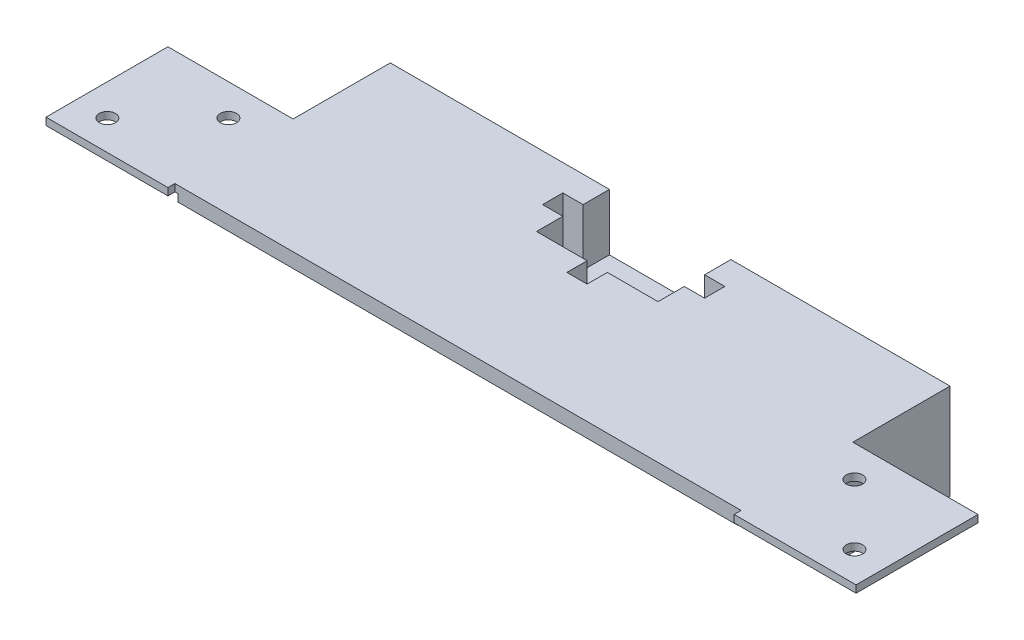
SolidWorks part; units mm, degrees
ref_plane "Alzado" through (0, 0, 0) normal (0, 0, 1) x (1, 0, 0)
ref_plane "Planta" through (0, 0, 0) normal (0, 1, 0) x (1, 0, 0)
ref_plane "Vista lateral" through (0, 0, 0) normal (1, 0, 0) x (0, 0, -1)
sketch "Croquis1" plane through (0, 0, 0) normal (0, 1, 0) x (1, 0, 0)
  line L0 (0, 16.8548) -> (0, -58.7896) construction
  line L1 (-69.5, -36.2916) -> (-69.5, -34.5716) construction
  line L2 (-100, -36.2916) -> (-69.5, -36.2916) construction
  line L3 (-100, -5.7916) -> (-100, -36.2916) construction
  line L4 (-69.5, -5.7916) -> (-100, -5.7916) construction
  line L5 (-69.5, -34.5716) -> (-69.5, -5.7916) construction
  line L17 (-69.5, -9.7916) -> (69.5, -9.7916) construction
  line L18 (69.5, -34.5716) -> (69.5, -5.7916) construction
  line L19 (69.5, -5.7916) -> (100, -5.7916) construction
  line L20 (100, -5.7916) -> (100, -36.2916) construction
  line L21 (100, -36.2916) -> (69.5, -36.2916) construction
  line L22 (69.5, -36.2916) -> (69.5, -34.5716) construction
  line L23 (69.5, -34.5716) -> (-69.5, -34.5716) construction
  circle A0 centre (-77.2782, -13.5698) radius 2 construction
  circle A1 centre (-92.2218, -28.5135) radius 2 construction
  circle A2 centre (-56.5, -26.2016) radius 2 construction
  circle A11 centre (56.5, -26.2016) radius 2 construction
  circle A12 centre (92.2218, -28.5135) radius 2 construction
  circle A13 centre (77.2782, -13.5698) radius 2 construction
  point P23 (0, -34.5716)
  point P28 (0, -9.7916)
sketch "Croquis4" plane through (0, 0, 0) normal (0, 1, 0) x (1, 0, 0)
  line L0 (69.5, -34.5716) -> (-69.5, -34.5716) construction
  line L1 (100, -36.2916) -> (69.5, -36.2916) construction
  line L2 (100, -5.7916) -> (100, -36.2916) construction
  line L3 (69.5, -5.7916) -> (100, -5.7916) construction
  line L5 (-69.5, -9.7916) -> (69.5, -9.7916) construction
  line L6 (0, 16.8548) -> (0, -58.7896) construction
  line L7 (69.5, -34.5716) -> (0, -34.5716) construction
  line L8 (100, -36.2916) -> (69.5, -36.2916) construction
  line L9 (100, -5.7916) -> (100, -36.2916) construction
  line L10 (69.5, -5.7916) -> (100, -5.7916) construction
  line L12 (0, -9.7916) -> (69.5, -9.7916) construction
  line L13 (0, 16.8548) -> (0, -58.7896) construction
  line L15 (69.5, -36.2916) -> (69.5, -34.5716) construction
  line L16 (69.5, -36.2916) -> (69.5, -34.5716) construction
  line L17 (100, -35.8916) -> (69.9, -35.8916)
  line L18 (69.9, -35.8916) -> (69.9, -34.1716)
  line L19 (69.9, -34.1716) -> (0, -34.1716)
  line L20 (100, -35.8916) -> (100, -5.7916)
  line L22 (100, -5.7916) -> (-100, -5.7916)
  line L23 (-69.9, -34.1716) -> (0, -34.1716)
  line L24 (-69.9, -35.8916) -> (-69.9, -34.1716)
  line L25 (-100, -35.8916) -> (-69.9, -35.8916)
  line L26 (-100, -35.8916) -> (-100, -5.7916)
  point P21 (0, -5.7916)
  dimension "D1" = 0.4
extrude "Saliente-Extruir1" add sketch "Croquis4" along normal blind 1.8
sketch "Croquis5" plane through (0, 1.8, 0) normal (0, 1, 0) x (1, 0, 0)
  line L0 (69.5, -34.5716) -> (-69.5, -34.5716) construction
  line L1 (69.5, -34.5716) -> (69.5, -5.7916) construction
  line L2 (-69.5, -9.7916) -> (69.5, -9.7916) construction
  line L3 (0, 16.8548) -> (0, -58.7896) construction
  line L4 (69.5, -34.5716) -> (0, -34.5716) construction
  line L5 (69.5, -34.5716) -> (69.5, -9.7916) construction
  line L6 (0, -9.7916) -> (69.5, -9.7916) construction
  line L7 (0, 16.8548) -> (0, -58.7896) construction
  line L11 (-69.1, -34.1716) -> (69.1, -34.1716)
  line L17 (-69.9, -34.1716) -> (69.9, -34.1716) construction
  line L18 (69.1, -34.1716) -> (69.1, -9.7916)
  line L19 (69.1, -34.5716) -> (69.1, -9.7916) construction
  line L20 (69.1, -9.7916) -> (69.1, -5.7916)
  line L21 (100, -5.7916) -> (-100, -5.7916) construction
  line L22 (69.1, -5.7916) -> (-69.1, -5.7916)
  line L23 (-69.1, -34.1716) -> (-69.1, -9.7916)
  line L24 (-69.1, -9.7916) -> (-69.1, -5.7916)
  point P20 (0, -10.2916)
  point P21 (0, -34.1716)
  point P23 (0, -5.7916)
  dimension "D1" = 0.4
extrude "Saliente-Extruir2" add sketch "Croquis5" against normal blind 1.8 from surface starting at face at (0, 0, 27.9366)
sketch "Croquis6" plane through (0, 1.8, 0) normal (0, 1, 0) x (1, 0, 0)
  line L0 (-69.5, -9.7916) -> (69.5, -9.7916) construction
  line L1 (0, -9.7916) -> (69.5, -9.7916) construction
  line L2 (0, 16.8548) -> (0, -58.7896) construction
  line L3 (0, 16.8548) -> (0, -58.7896) construction
  line L4 (69.5, -34.5716) -> (69.5, -5.7916) construction
  line L5 (69.5, -9.7916) -> (69.5, -5.7916) construction
  line L14 (-69.1, -9.1916) -> (69.1, -9.1916)
  line L15 (69.1, -9.1916) -> (69.1, -5.7916)
  line L16 (69.1, -9.7916) -> (69.1, -5.7916) construction
  line L17 (0, -9.1916) -> (69.5, -9.1916) construction
  line L18 (69.1, -5.7916) -> (-69.1, -5.7916)
  line L19 (100, -5.7916) -> (-100, -5.7916) construction
  line L20 (-69.1, -9.1916) -> (-69.1, -5.7916)
  point P17 (0, -5.7916)
  dimension "D1" = 0.6
  dimension "D2" = 0.4
extrude "Saliente-Extruir3" add sketch "Croquis6" against normal blind 20 from surface starting at face at (0, -1.8, 19.9816)
sketch "Croquis7" plane through (0, 0, 5.7916) normal (0, 0, -1) x (-1, 0, 0)
  line L0 (0, 22.365) -> (0, -38.5622) construction
  line L1 (0, 1.8) -> (75, 1.8)
  line L2 (-100, 1.8) -> (100, 1.8) construction
  line L3 (75, 1.8) -> (75, -21.8)
  line L4 (-69.1, -21.8) -> (69.1, -21.8) construction
  line L5 (75, -21.8) -> (0, -21.8)
  dimension "D1" = 75
sketch "Croquis8" plane through (0, 0, 5.7916) normal (0, 0, -1) x (-1, 0, 0)
  line L0 (0, 22.365) -> (0, -38.5622) construction
  line L1 (0, 22.365) -> (0, -38.5622) construction
  line L2 (-69.1, 1.8) -> (69.1, 1.8)
  line L3 (0, 1.8) -> (75, 1.8) construction
  line L4 (69.1, 1.8) -> (69.1, -21.8)
  line L5 (69.1, -21.8) -> (-69.1, -21.8)
  line L6 (-69.1, 1.8) -> (-69.1, -21.8)
  point P12 (0, 1.8)
  point P13 (0, -21.8)
extrude "Saliente-Extruir4" add sketch "Croquis8" along normal blind 24
sketch "Croquis9" plane through (0, 1.8, 0) normal (0, 1, 0) x (1, 0, 0)
  line L0 (0, 16.8548) -> (0, -58.7896) construction
  line L1 (0, 33.1742) -> (0, -58.7896) construction
  line L2 (15, 18.2084) -> (-15, 18.2084)
  line L3 (-69.1, 18.2084) -> (69.1, 18.2084) construction
  line L4 (-15, 18.2084) -> (-15, 0.2084)
  line L5 (-15, 0.2084) -> (15, 0.2084)
  line L6 (15, 18.2084) -> (15, 0.2084)
  point P10 (0, 0.2084)
  point P11 (0, 18.2084)
  dimension "D1" = 18
  dimension "D2" = 15
extrude "Cortar-Extruir1" cut sketch "Croquis9" against normal blind 14
sketch "Croquis10" plane through (0, -12.2, 0) normal (0, 1, 0) x (1, 0, 0)
  line L0 (0, 16.8548) -> (0, -58.7896) construction
  line L1 (0, 22.5663) -> (0, -58.7896) construction
  line L2 (15, 18.2084) -> (-15, 18.2084) construction
  line L3 (15, 18.2084) -> (-15, 18.2084) construction
  circle A0 centre (-4.75, 10.2084) radius 1
  circle A1 centre (4.75, 10.2084) radius 1
  dimension "D1" = 2
  dimension "D2" = 4.75
  dimension "D3" = 8
sketch "Croquis11" plane through (0, 1.8, 0) normal (0, 1, 0) x (1, 0, 0)
  circle A0 centre (92.2218, -28.5135) radius 2 construction
  circle A1 centre (77.2782, -13.5698) radius 2 construction
  circle A2 centre (-77.2782, -13.5698) radius 2 construction
  circle A3 centre (-92.2218, -28.5135) radius 2 construction
  circle A4 centre (92.2218, -28.5135) radius 2
  circle A5 centre (77.2782, -13.5698) radius 2
  circle A6 centre (-77.2782, -13.5698) radius 2
  circle A7 centre (-92.2218, -28.5135) radius 2
extrude "Cortar-Extruir2" cut sketch "Croquis11" against normal through all
sketch "Croquis12" plane through (0, -21.8, 0) normal (0, 1, 0) x (1, 0, 0)
  line L0 (-17.044, 0.2084) -> (17.044, 0.2084) construction
  text T0 "NUT BOT" font "Century Gothic" height 6
  point P4 (-12.5109, 0)
  point P5 (18.433, 0)
  point P6 (-15.0403, 0)
  point P7 (0, 0.2084)
  point P8 (1.7249, 0.2084)
  point P9 (0, 0.2084)
  point P10 (17.044, 0)
extrude "Cortar-Extruir4" cut sketch "Croquis12" along normal blind 1
sketch "Croquis14" plane through (0, 1.8, 0) normal (0, 1, 0) x (1, 0, 0)
  line L0 (15, 0.2084) -> (15, 18.2084) construction
  line L1 (-15, 18.2084) -> (-15, 0.2084) construction
  line L2 (15, 0.2084) -> (15, 18.2084) construction
  line L3 (-15, 18.2084) -> (-15, 0.2084) construction
  line L4 (-18.7981, 9.2084) -> (18.7981, 9.2084) construction
  line L5 (0, 20.6624) -> (0, -12.0045) construction
  line L7 (20, 6.7084) -> (15, 6.7084)
  line L8 (-20, 11.7084) -> (-15, 11.7084)
  line L9 (-20, 11.7084) -> (-20, 6.7084)
  line L10 (-20, 6.7084) -> (-15, 6.7084)
  line L11 (-15, 11.7084) -> (-15, 6.7084)
  line L12 (-20, 11.7084) -> (-15, 6.7084) construction
  line L13 (-20, 6.7084) -> (-15, 11.7084) construction
  line L14 (15, 11.7084) -> (15, 6.7084)
  line L19 (-15, 0.2084) -> (15, 0.2084) construction
  line L20 (2.5, -4.7916) -> (-2.5, -4.7916)
  line L21 (2.5, -4.7916) -> (2.5, 0.2084)
  line L22 (2.5, 0.2084) -> (-2.5, 0.2084)
  line L23 (-2.5, -4.7916) -> (-2.5, 0.2084)
  line L24 (2.5, -4.7916) -> (-2.5, 0.2084) construction
  line L25 (2.5, 0.2084) -> (-2.5, -4.7916) construction
  line L26 (20, 11.7084) -> (15, 11.7084)
  line L27 (20, 11.7084) -> (20, 6.7084)
  point P6 (-15, 9.2084)
  point P8 (0, 9.2084)
  point P11 (0, 0)
  point P12 (0, 0)
  point P13 (-17.5, 9.2084)
  point P22 (17.5, 9.2084)
  point P23 (0, -2.2916)
  dimension "D1" = 5
  dimension "D2" = 5
  dimension "D3" = 5
  dimension "D4" = 5
extrude "Cortar-Extruir5" cut sketch "Croquis14" against normal up to surface (14 mm away) up to face at (0, -12.2, -9.2084)
